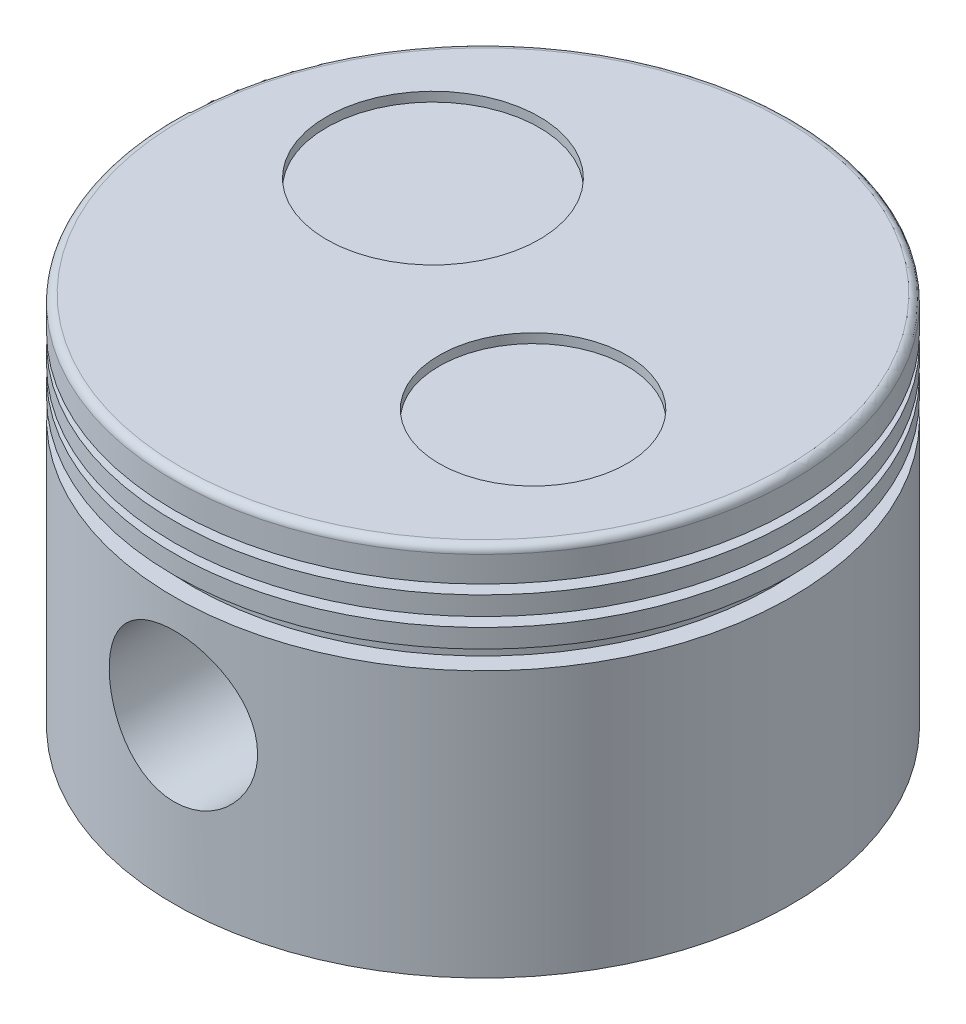
SolidWorks part; units mm, degrees
ref_plane "Front Plane" through (0, 0, 0) normal (0, 0, 1) x (1, 0, 0)
ref_plane "Top Plane" through (0, 0, 0) normal (0, 1, 0) x (1, 0, 0)
ref_plane "Right Plane" through (0, 0, 0) normal (1, 0, 0) x (0, 0, -1)
other "Configuration Table"
sketch "Sketch1" plane through (0, 0, 0) normal (0, 0, 1) x (1, 0, 0)
  line L0 (0, -60) -> (0, -40) construction
  line L1 (0, 33.8) -> (48.1, 33.8)
  line L2 (49.3, 32.6) -> (49.3, -26)
  line L3 (49.3, -26) -> (44.3, -26)
  line L4 (44.3, -26) -> (44.3, 19)
  line L5 (44.3, 19) -> (0, 19)
  line L6 (0, 19) -> (0, 33.8)
  arc A0 (48.1, 33.8) -> (49.3, 32.6) centre (48.1, 32.6) cw
revolve "Piston Body" add sketch "Sketch1" angle 360 about L0
sketch "Sketch2" plane through (0, 0, 0) normal (0, 0, 1) x (1, 0, 0)
  line L0 (-17, 19.5) -> (-17, -1.7)
  line L1 (-1.7, -17) -> (1.7, -17)
  line L2 (17, -1.7) -> (17, 19.5)
  line L3 (17, 19.5) -> (-17, 19.5)
  arc A0 (-17, -1.7) -> (-1.7, -17) centre (-1.7, -1.7) ccw
  arc A1 (1.7, -17) -> (17, -1.7) centre (1.7, -1.7) ccw
extrude "Pin Boss Front" add sketch "Sketch2" along normal blind 31.5 from offset 13
sketch "Sketch3" plane through (0, 0, 0) normal (0, 0, 1) x (1, 0, 0)
  line L0 (-17, 19.5) -> (-17, -1.7)
  line L1 (-1.7, -17) -> (1.7, -17)
  line L2 (17, -1.7) -> (17, 19.5)
  line L3 (17, 19.5) -> (-17, 19.5)
  arc A0 (-17, -1.7) -> (-1.7, -17) centre (-1.7, -1.7) ccw
  arc A1 (1.7, -17) -> (17, -1.7) centre (1.7, -1.7) ccw
extrude "Pin Boss Rear" add sketch "Sketch3" along normal blind 31.5 from offset 44.5 offset against normal yes
sketch "Sketch4" plane through (0, 0, 0) normal (0, 0, 1) x (1, 0, 0)
  circle A0 centre (0, 0) radius 11.85
extrude "Pin Bore" cut sketch "Sketch4" against normal through all and the other way through all
sketch "Sketch5" plane through (0, 0, 0) normal (0, 0, 1) x (1, 0, 0)
  line L0 (0, -60) -> (0, -40) construction
  line L1 (46.4, 27) -> (50.5, 27)
  line L2 (50.5, 27) -> (50.5, 28.5)
  line L3 (50.5, 28.5) -> (46.4, 28.5)
  line L4 (46.4, 28.5) -> (46.4, 27)
  line L5 (46.4, 22.5) -> (50.5, 22.5)
  line L6 (50.5, 22.5) -> (50.5, 24)
  line L7 (50.5, 24) -> (46.4, 24)
  line L8 (46.4, 24) -> (46.4, 22.5)
  line L9 (46.4, 16.5) -> (50.5, 16.5)
  line L10 (50.5, 16.5) -> (50.5, 19.5)
  line L11 (50.5, 19.5) -> (46.4, 19.5)
  line L12 (46.4, 19.5) -> (46.4, 16.5)
revolve "Ring Grooves" cut sketch "Sketch5" angle 360 about L0
sketch "Sketch6" plane through (0, 33.8, 0) normal (0, 1, 0) x (1, 0, 0)
  circle A0 centre (-20, 12) radius 17
  circle A1 centre (20, -12) radius 15
extrude "Valve Reliefs" cut sketch "Sketch6" against normal blind 1.5
ref_axis "Pin Axis" through (0, 0, -199.0801) along (0, 0, 1)
ref_axis "Bore Axis" through (0, 189.2889, 0) along (0, -1, 0)
